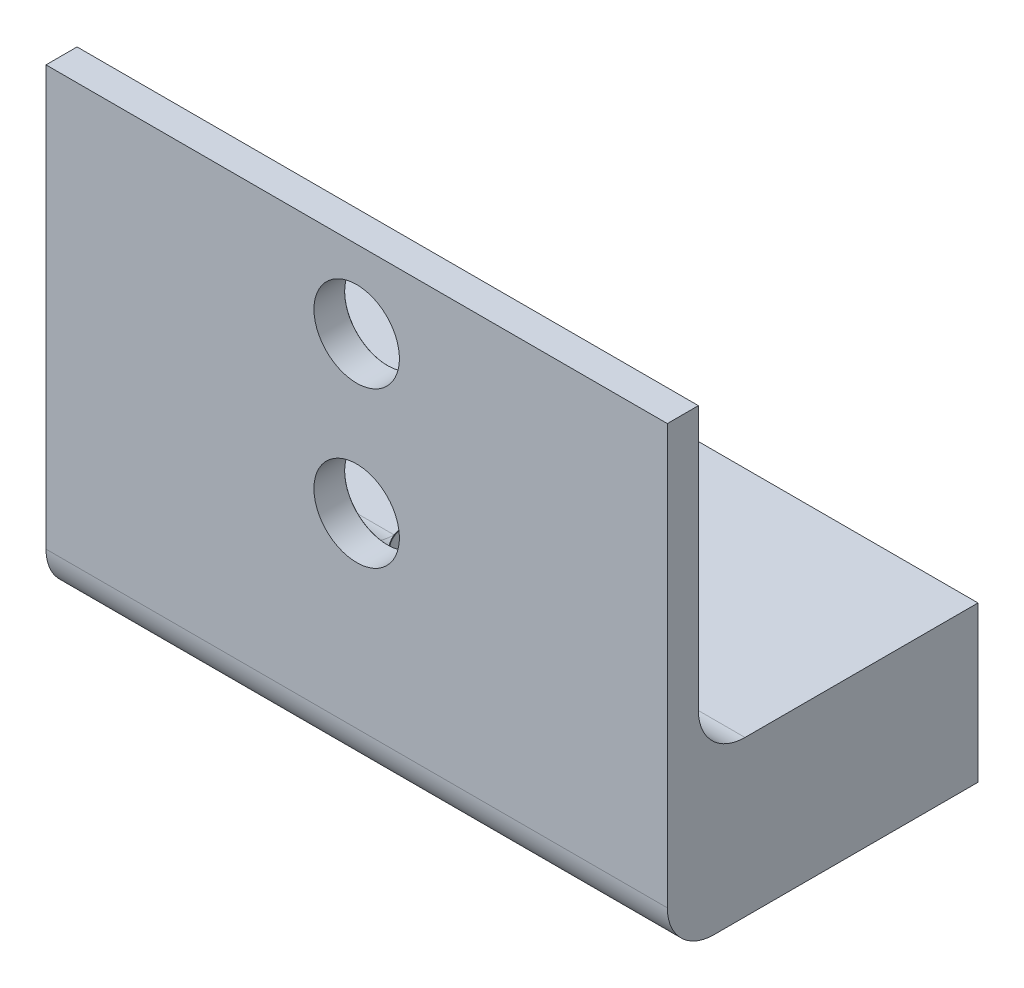
SolidWorks part; units mm, degrees
ref_plane "Plan de face" through (0, 0, 0) normal (0, 0, 1) x (1, 0, 0)
ref_plane "Plan de dessus" through (0, 0, 0) normal (0, 1, 0) x (1, 0, 0)
ref_plane "Plan de droite" through (0, 0, 0) normal (1, 0, 0) x (0, 0, -1)
sketch "Profil Base" plane through (0, 0, 0) normal (0, 1, 0) x (1, 0, 0)
  line L1 (-20, 10) -> (20, 10)
  line L2 (-20, 10) -> (-20, -10)
  line L3 (-20, -10) -> (20, -10)
  line L4 (20, 10) -> (20, -10)
  line L5 (-20, 10) -> (20, -10) construction
  line L6 (-20, -10) -> (20, 10) construction
  point P0 (0, 0)
  dimension "D1" = 40
  dimension "D2" = 20
extrude "Base" add sketch "Profil Base" along normal mid plane 10
sketch "Profil Vertical" plane through (0, 0, 10) normal (0, 0, 1) x (1, 0, 0)
  line L1 (-20, -5) -> (20, -5)
  line L2 (-20, -5) -> (-20, 25)
  line L3 (-20, 25) -> (20, 25)
  line L4 (20, -5) -> (20, 25)
  dimension "D1" = 40
  dimension "D2" = 30
extrude "Vertical" add sketch "Profil Vertical" against normal blind 2
hole_wizard "Perçage Base" positions "Esquisse3" profile "Esquisse4" hole size "M5" standard "Ansi Metric" end condition up to next
sketch "Esquisse3" plane through (0, 5, 0) normal (0, 1, 0) x (1, 0, 0)
  line L0 (0, 0) -> (-8.8138, 0) construction
  line L1 (-8.8138, 0) -> (10.8655, 0) construction
  point P0 (0, -4)
  point P2 (0, 4)
  point P12 (0, 0)
  dimension "D1" = 8
sketch "Esquisse4" plane through (0, 5, 4) normal (1, 0, 0) x (0, 0, 1)
  line L0 (0, 0) -> (0, 10)
  line L1 (0, 10) -> (2.75, 10)
  line L2 (2.75, 10) -> (2.75, 0.025)
  line L3 (2.75, 0.025) -> (2.775, 0)
  line L5 (2.775, 0) -> (0, 0)
  line L6 (-2.75, 0.025) -> (-2.775, 0) construction
  line L11 (0, -6.35) -> (0, 107.95) construction
  dimension "Diamètre du perçage jusqu'au prochain" = 5.5
  dimension "Profondeur du perçage jusqu'au prochain" = 10
  dimension "Diamètre du fraisage entrant" = 5.55
  dimension "Angle du fraisage entrant" = 90
hole_wizard "Perçage Vertical" positions "Esquisse7" profile "Esquisse6" hole size "M5" standard "Ansi Metric" end condition up to next
sketch "Esquisse7" plane through (0, 0, 8) normal (0, 0, -1) x (-1, 0, 0)
  line L0 (-5.6639, 15) -> (5.4616, 15) construction
  point P0 (0, 10)
  point P2 (0, 20)
  point P11 (0, 0)
  dimension "D1" = 10
sketch "Esquisse6" plane through (0, 10, 8) normal (1, 0, 0) x (0, 1, 0)
  line L0 (0, 0) -> (0, 2)
  line L1 (0, 2) -> (2.75, 2)
  line L2 (2.75, 2) -> (2.75, 0.025)
  line L3 (2.75, 0.025) -> (2.775, 0)
  line L5 (2.775, 0) -> (0, 0)
  line L6 (-2.75, 0.025) -> (-2.775, 0) construction
  line L11 (0, -6.35) -> (0, 107.95) construction
  dimension "Diamètre du perçage jusqu'au prochain" = 5.5
  dimension "Profondeur du perçage jusqu'au prochain" = 2
  dimension "Diamètre du fraisage entrant" = 5.55
  dimension "Angle du fraisage entrant" = 90
fillet "Congé1" radius 3 2 edges at (0, -5, 10) (0, 5, 8)
